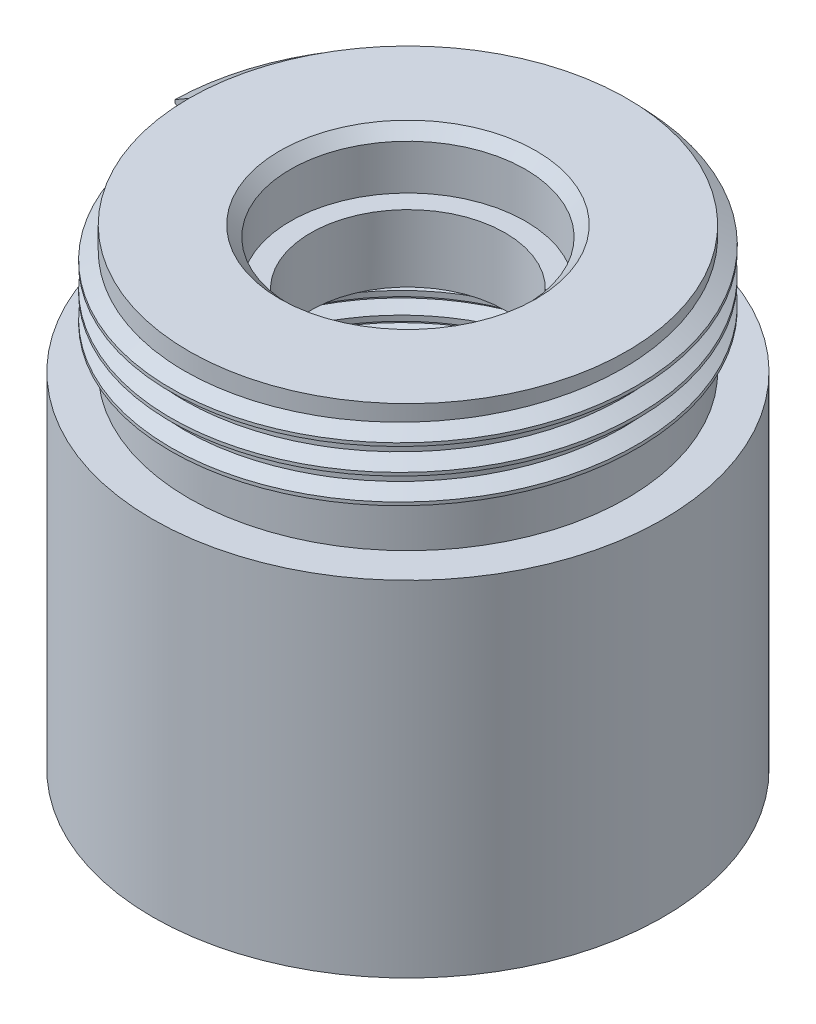
SolidWorks part; units mm, degrees
ref_plane "Front Plane" through (0, 0, 0) normal (0, 0, 1) x (1, 0, 0)
ref_plane "Top Plane" through (0, 0, 0) normal (0, 1, 0) x (1, 0, 0)
ref_plane "Right Plane" through (0, 0, 0) normal (1, 0, 0) x (0, 0, -1)
sketch "Sketch1" plane through (0, 0, 0) normal (0, 1, 0) x (1, 0, 0)
  circle A0 centre (0, 0) radius 5.975
  dimension "D1" = 11.95
extrude "Boss-Extrude1" add sketch "Sketch1" along normal blind 8.06
sketch "Sketch2" plane through (0, 8.06, 0) normal (0, 1, 0) x (1, 0, 0)
  circle A0 centre (0, 0) radius 5.125
  dimension "D1" = 10.25
extrude "Boss-Extrude2" add sketch "Sketch2" along normal blind 2.98
thread "Thread1" pitch 0.6 method extrude profile "Thread Profile1" start angle 0, offset 0, length 2, pitch 0.6, diameter 10.25
ref_plane "Plane1" through (-5.125, 11.04, 0) normal (0, 0, 1) x (-1, 0, 0)
sketch "Thread Profile1" plane through (-5.125, 11.04, 0) normal (0, 0, 1) x (-1, 0, 0)
  line L0 (0, 0) -> (0, 0.6) construction
  line L1 (0, 0) -> (0.3248, 0.1875)
  line L2 (0.3248, 0.1875) -> (0.3248, 0.2625)
  line L3 (0.3248, 0.2625) -> (0, 0.45)
  line L4 (0.3248, 0.225) -> (0, 0.225) construction
  line L11 (0, 0) -> (0, 0.45)
  point P2 (0, 0)
  dimension "Pitch" = 0.6
  dimension "Profile_Angle" = 60
  dimension "Profile_Land" = 0.075
  dimension "Profile_Height" = 0.3248
sketch "Sketch7" plane through (0, 0, 0) normal (0, -1, 0) x (1, 0, 0)
  circle A0 centre (0, 0) radius 4.275
  dimension "D1" = 8.55
extrude "Cut-Extrude1" cut sketch "Sketch7" against normal blind 8.17
sketch "Sketch8" plane through (0, 8.17, 0) normal (0, -1, 0) x (1, 0, 0)
  circle A0 centre (0, 0) radius 2.275
  dimension "D1" = 4.55
extrude "Cut-Extrude2" cut sketch "Sketch8" against normal through all
sketch "Sketch9" plane through (0, 11.04, 0) normal (0, 1, 0) x (1, 0, 0)
  circle A0 centre (0, 0) radius 2.75
  dimension "D1" = 5.5
extrude "Cut-Extrude3" cut sketch "Sketch9" against normal blind 1.3
chamfer "Chamfer1" distance 0.25 angle 45 1 edges at (0, 11.04, 2.75)
thread "Thread2" pitch 0.5 method cut profile "Thread Profile2" start angle 0, offset 0, length 0, pitch 0.5, diameter 8.55
ref_plane "Plane2" through (4.275, 0, 0) normal (0, 0, 1) x (1, 0, 0)
sketch "Thread Profile2" plane through (4.275, 0, 0) normal (0, 0, 1) x (1, 0, 0)
  line L0 (0, 0) -> (0, 0.5) construction
  line L1 (0, 0) -> (0.2706, 0.1562)
  line L2 (0.2706, 0.1562) -> (0.2706, 0.2187)
  line L3 (0.2706, 0.2187) -> (0, 0.375)
  line L4 (0.2706, 0.1875) -> (0, 0.1875) construction
  line L11 (0, 0) -> (0, 0.375)
  point P2 (0, 0)
  dimension "Pitch" = 0.5
  dimension "Profile_Angle" = 60
  dimension "Profile_Land" = 0.0625
  dimension "Profile_Height" = 0.2706
